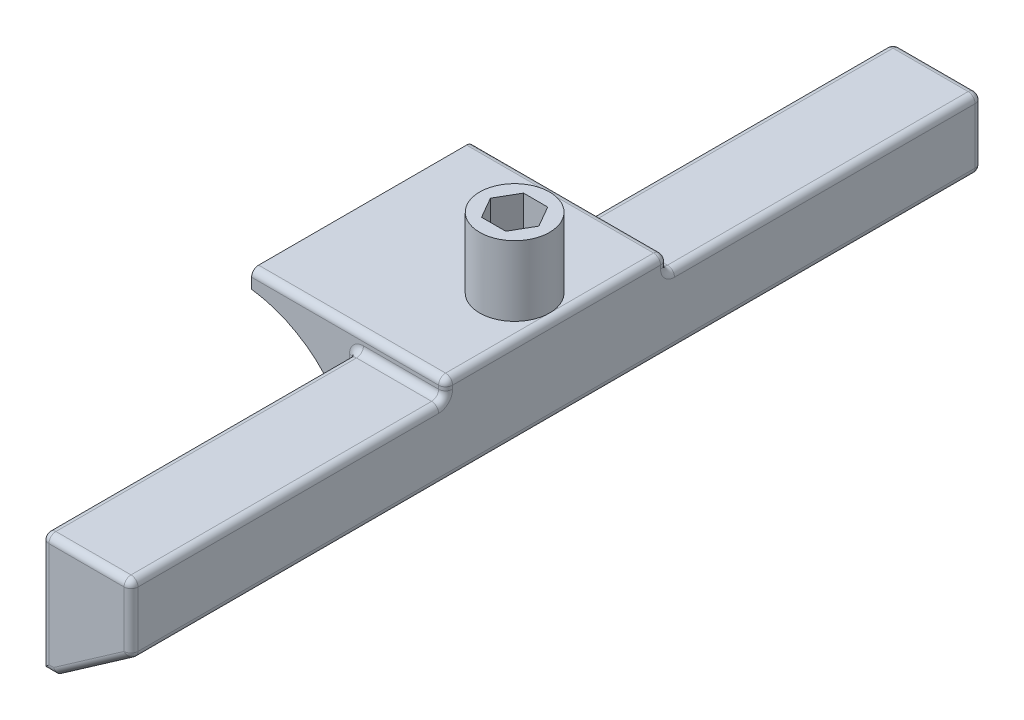
SolidWorks part; units mm, degrees
ref_plane "Front Plane" through (0, 0, 0) normal (0, 0, 1) x (1, 0, 0)
ref_plane "Top Plane" through (0, 0, 0) normal (0, 1, 0) x (1, 0, 0)
ref_plane "Right Plane" through (0, 0, 0) normal (1, 0, 0) x (0, 0, -1)
sketch "Sketch1" plane through (0, 0, 0) normal (0, 1, 0) x (1, 0, 0)
  line L0 (-4, 4) -> (-4, -239.5)
  line L1 (0, 0) -> (17.5, 0)
  line L2 (0, 0) -> (0, -235.5)
  line L3 (0, -235.5) -> (17.5, -235.5)
  line L4 (17.5, 0) -> (17.5, -235.5)
  line L5 (-4, -239.5) -> (21.5, -239.5)
  line L6 (21.5, 4) -> (21.5, -239.5)
  line L7 (-4, 4) -> (21.5, 4)
  dimension "D1" = 17.5
  dimension "D2" = 235.5
  dimension "D3" = 4
extrude "motor -panel connector " add sketch "Sketch1" along normal blind 34
sketch "Sketch3" plane through (0, 34, 0) normal (0, 1, 0) x (1, 0, 0)
  line L1 (-4, 4) -> (21.5, 4)
  line L2 (-4, 4) -> (-4, -239.5)
  line L3 (-4, -239.5) -> (21.5, -239.5)
  line L4 (21.5, 4) -> (21.5, -239.5)
extrude "motor-panel connecctor base" add sketch "Sketch3" against normal blind 4
sketch "Sketch4" plane through (0, 0, 239.5) normal (0, 0, 1) x (1, 0, 0)
  line L0 (0, 0) -> (21.5, 15)
  line L1 (21.5, 34) -> (21.5, 0) construction
  line L2 (21.5, 15) -> (21.5, 0)
  line L3 (21.5, 0) -> (0, 0)
  dimension "D1" = 19
extrude "up down connect cut" cut sketch "Sketch4" against normal blind 250
sketch "Sketch5" plane through (-4, 0, 0) normal (-1, 0, 0) x (0, 0, 1)
  line L0 (-4, 0) -> (239.5, 0) construction
  line L1 (94, 31) -> (141.5, 31)
  line L2 (94, 31) -> (94, 0)
  line L3 (94, 0) -> (141.5, 0)
  line L4 (141.5, 31) -> (141.5, 0)
  line L5 (239.5, 34) -> (239.5, 0) construction
  line L6 (-4, 34) -> (-4, 0) construction
  dimension "D1" = 98
  dimension "D2" = 98
  dimension "D3" = 31
extrude "cut to nail part" cut sketch "Sketch5" against normal blind 5
sketch "Sketch6" plane through (0, 34, 0) normal (0, 1, 0) x (1, 0, 0)
  line L0 (21.5, -239.5) -> (21.5, 4) construction
  line L1 (21.5, -86) -> (-34, -86)
  line L2 (21.5, -86) -> (21.5, -149.5)
  line L3 (21.5, -149.5) -> (-34, -149.5)
  line L4 (-34, -86) -> (-34, -149.5)
  line L5 (-4, 4) -> (-4, -239.5) construction
  line L6 (-4, -239.5) -> (21.5, -239.5) construction
  line L7 (21.5, 4) -> (-4, 4) construction
  point P8 (-34, -117.75)
  dimension "D1" = 30
  dimension "D2" = 90
  dimension "D3" = 90
extrude "panel connector" add sketch "Sketch6" along normal blind 5
sketch "Sketch7" plane through (0, 39, 0) normal (0, 1, 0) x (1, 0, 0)
  line L0 (21.5, -149.5) -> (21.5, -86) construction
  line L1 (21.5, 4) -> (-4, 4) construction
  line L10 (12.9641, -123.75) -> (16.4282, -117.75)
  line L11 (16.4282, -117.75) -> (12.9641, -111.75)
  line L12 (12.9641, -111.75) -> (6.0359, -111.75)
  line L13 (6.0359, -111.75) -> (2.5718, -117.75)
  line L14 (2.5718, -117.75) -> (6.0359, -123.75)
  line L15 (6.0359, -123.75) -> (12.9641, -123.75)
  circle A0 centre (9.5, -117.75) radius 10
  circle A1 centre (9.5, -117.75) radius 6 construction
  dimension "D1" = 20
  dimension "D2" = 12
  dimension "D3" = 121.75
  dimension "D4" = 6
extrude "Boss-Extrude4" add sketch "Sketch7" along normal blind 20
sketch "Sketch8" plane through (0, 0, 149.5) normal (0, 0, 1) x (1, 0, 0)
  line L0 (-34, 34) -> (-4, 34)
  line L1 (-4, 34) -> (-4, 0)
  arc A0 (-4, 0) -> (-34, 34) centre (-38.2667, 0) ccw
extrude "Boss-Extrude5" add sketch "Sketch8" against normal blind 5
sketch "Sketch13" plane through (0, 0, 86) normal (0, 0, -1) x (-1, 0, 0)
  line L1 (4, 0) -> (4, 34)
  line L2 (4, 34) -> (34, 34)
  arc A0 (34, 34) -> (4, 0) centre (39.8204, -1.3709) ccw
extrude "Boss-Extrude6" add sketch "Sketch13" against normal blind 5
fillet "Fillet1" radius 2 24 edges at (21.5, 34, 194.5) (21.5, 36.5, 149.5) (21.5, 39, 117.75) (21.5, 36.5, 86) (21.5, 34, 41) (21.5, 24.5, -4) (21.5, 15, 117.75) (21.5, 24.5, 239.5) (-4, 17, 149.5) (-4, 17, 86) (-4, 34, 194.5) (8.75, 34, 149.5) (-4, 17, 239.5) (8.75, 34, 239.5) (10.75, 7.5, 239.5) (-2, 0, 239.5) (-4, 34, 41) (8.75, 34, 86) (8.75, 34, -4) (-4, 17, -4) (-2, 0, -4) (10.75, 7.5, -4) (-6.25, 39, 149.5) (-6.25, 39, 86)
